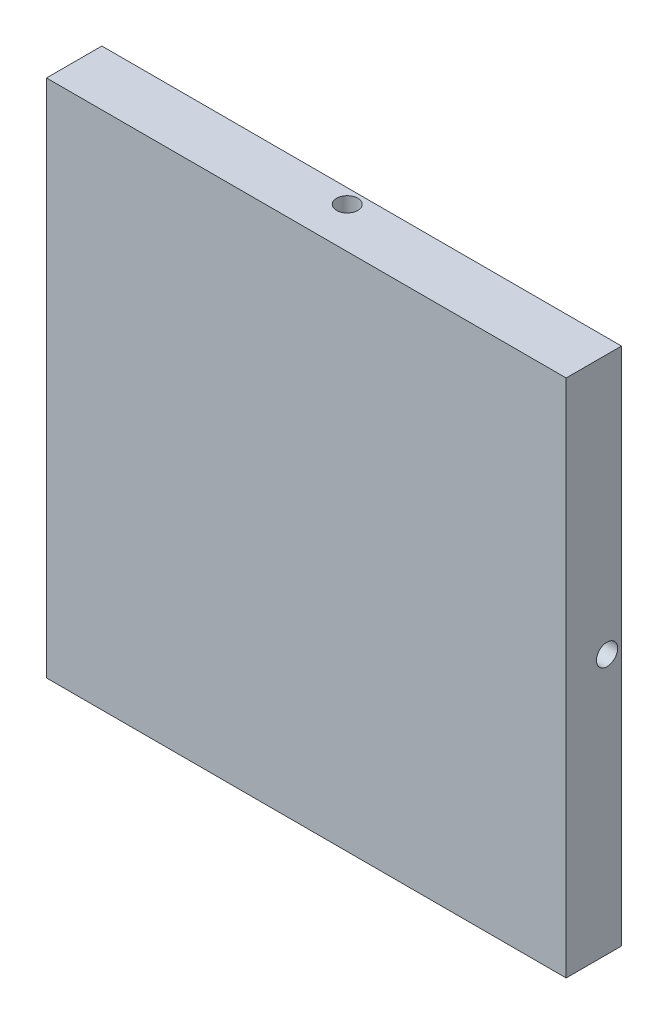
SolidWorks part; units mm, degrees
ref_plane "Front Plane" through (0, 0, 0) normal (0, 0, 1) x (1, 0, 0)
ref_plane "Top Plane" through (0, 0, 0) normal (0, 1, 0) x (1, 0, 0)
ref_plane "Right Plane" through (0, 0, 0) normal (1, 0, 0) x (0, 0, -1)
sketch "Sketch1" plane through (0, 0, 0) normal (0, 0, 1) x (1, 0, 0)
  line L0 (0, 0) -> (-19.5465, -53.7034) construction
  line L1 (-85.725, 85.725) -> (85.725, 85.725)
  line L2 (-85.725, 85.725) -> (-85.725, -85.725)
  line L3 (-85.725, -85.725) -> (85.725, -85.725)
  line L4 (85.725, 85.725) -> (85.725, -85.725)
  line L5 (0, 0) -> (0, -76.9938) construction
  line L6 (-27.4443, 76.9938) -> (31.5245, 76.9938) construction
  circle A0 centre (0, 0) radius 76.9938
  circle A1 centre (-19.5465, -53.7034) radius 3.175
  circle A2 centre (0, 0) radius 3.175
  circle A3 centre (-36.7353, 43.7794) radius 3.175
  circle A4 centre (56.2818, 9.924) radius 3.175
  circle A5 centre (-73.025, 73.025) radius 3.175
  circle A6 centre (73.025, 73.025) radius 3.175
  circle A7 centre (73.025, -73.025) radius 3.175
  circle A8 centre (-73.025, -73.025) radius 3.175
  point P12 (0, 85.725)
  point P18 (0, 0)
  point P23 (-85.725, 0)
  point P29 (0, 0)
  dimension "D1" = 153.9875
  dimension "D4" = 6.35
  dimension "D5" = 6.35
  dimension "D7" = 6.35
  dimension "D2" = 57.15
  dimension "D3" = 20
  dimension "D8" = 12.7
  dimension "D9" = 90
  dimension "D10" = 12.7
  dimension "D11" = 4
  dimension "D12" = 85.725
  dimension "D13" = 8.7312
  dimension "D6" = 3
extrude "Boss-Extrude1" add sketch "Sketch1" along normal blind 8.7312 contours L4 L1 L2 L3 A8 A7 A6 A5 A0 | A6 | A5 | A8 | A7 | A1 | A3 | A4 | A0 A4 A3 A2 A1 | A2 region at (0, 83.3003, 0) region at (-74.816, 0, 0) region at (-19.5465, -53.7034, 0) region at (0, 0, 0) region at (-36.7353, 43.7794, 0) region at (56.2818, 9.924, 0) region at (-73.025, 73.025, 0) region at (73.025, 73.025, 0) region at (73.025, -73.025, 0) region at (-73.025, -73.025, 0)
extrude "Boss-Extrude2" add sketch "Sketch1<3>" against normal blind 9.525 contours L4 L1 L2 L3 A8 A7 A6 A5 A0 | A4 | A1 | A2 | A3 region at (0, 83.3003, 0) region at (-19.5465, -53.7034, 0) region at (0, 0, 0) region at (-36.7353, 43.7794, 0) region at (56.2818, 9.924, 0)
sketch "Sketch1<3>" plane through (0, 0, 0) normal (0, 0, 1) x (1, 0, 0) same geometry as "Sketch1"
extrude "Boss-Extrude3" add sketch "Sketch1<4>" against normal blind 18.3515 contours A2 region at (0, 0, 0)
sketch "Sketch1<4>" plane through (0, 0, 0) normal (0, 0, 1) x (1, 0, 0) same geometry as "Sketch1"
sketch "Sketch2" plane through (0, 85.725, 0) normal (0, 1, 0) x (1, 0, 0)
  line L0 (-85.725, 9.525) -> (85.725, 9.525) construction
  circle A0 centre (0, 4.7625) radius 3.5
  dimension "D1" = 7
  dimension "D2" = 4.7625
extrude "Cut-Extrude1" cut sketch "Sketch2" against normal up to next
pattern_circular "CirPattern1" count 4 over 360 about axis through (0, 0, -9.525) along (0, 0, 1) of "Cut-Extrude1"
sketch "Sketch4" plane through (0, 0, 0) normal (0, 0, -1) x (-1, 0, 0)
  line L0 (-67.236, 0) -> (-36.9732, 0) construction
  line L1 (-67.236, 1.5875) -> (-36.9732, 1.5875)
  line L2 (-67.236, -1.5875) -> (-36.9732, -1.5875)
  arc A0 (-67.236, 1.5875) -> (-67.236, -1.5875) centre (-67.236, 0) ccw
  arc A1 (-36.9732, -1.5875) -> (-36.9732, 1.5875) centre (-36.9732, 0) ccw
  point P2 (-52.1046, 0)
  point P7 (-52.1046, 0)
  point P8 (0, 0)
  dimension "D1" = 3.175
extrude "Cut-Extrude2" cut sketch "Sketch4" against normal blind 5.08
fillet "Fillet3" radius 3.175 4 edges at (52.1046, 1.5875, 0) (35.3857, 0, 0) (52.1046, -1.5875, 0) (68.8235, 0, 0)
